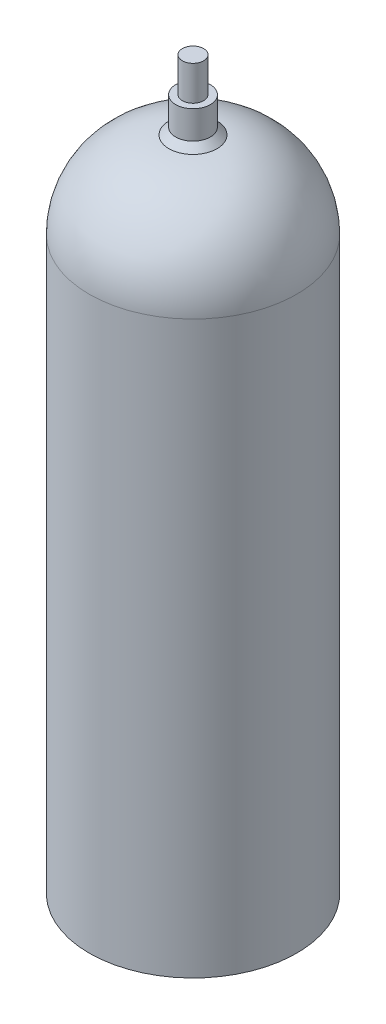
SolidWorks part; units mm, degrees
ref_plane "Front Plane" through (0, 0, 0) normal (0, 0, 1) x (1, 0, 0)
ref_plane "Top Plane" through (0, 0, 0) normal (0, 1, 0) x (1, 0, 0)
ref_plane "Right Plane" through (0, 0, 0) normal (1, 0, 0) x (0, 0, -1)
sketch "Sketch1" plane through (0, 0, 0) normal (0, 0, 1) x (1, 0, 0)
  line L0 (0, 337.1084) -> (0, -47.8206) construction
  line L1 (0, 248.389) -> (6.35, 248.389)
  line L2 (6.35, 248.389) -> (6.35, 222.989)
  line L3 (38.1, 191.239) -> (38.1, -18.311)
  line L4 (38.1, -18.311) -> (0, -18.311)
  line L5 (0, 248.389) -> (0, -18.311)
  line L7 (-19.606, -18.311) -> (74.8396, -18.311) construction
  arc A2 (38.1, 191.239) -> (6.35, 222.989) centre (6.35, 191.239) ccw
  point P8 (3.81, 19.6282)
  point P10 (12.7, 19.5447)
  point P11 (0, 337.1084)
  point P14 (0, -47.8206)
  point P16 (38.1, -18.311)
  point P17 (74.8396, -18.311)
  dimension "D2" = 25.4
  dimension "D3" = 266.7
  dimension "D1" = 6.35
  dimension "D4" = 38.1
revolve "Revolve1" add sketch "Sketch1" angle 360 about L0
chamfer "Chamfer2" distance 2.38 angle 45 1 edges at (0, 222.989, 6.35)
sketch "Sketch2" plane through (0, 248.389, 0) normal (0, 1, 0) x (1, 0, 0)
  circle A2 centre (0, 0) radius 3.902
  circle A3 centre (0, 0) radius 6.35 construction
  circle A4 centre (0, 0) radius 6.35
  dimension "D1" = 2.448
extrude "Cut-Extrude1" cut sketch "Sketch2" against normal blind 12.7
